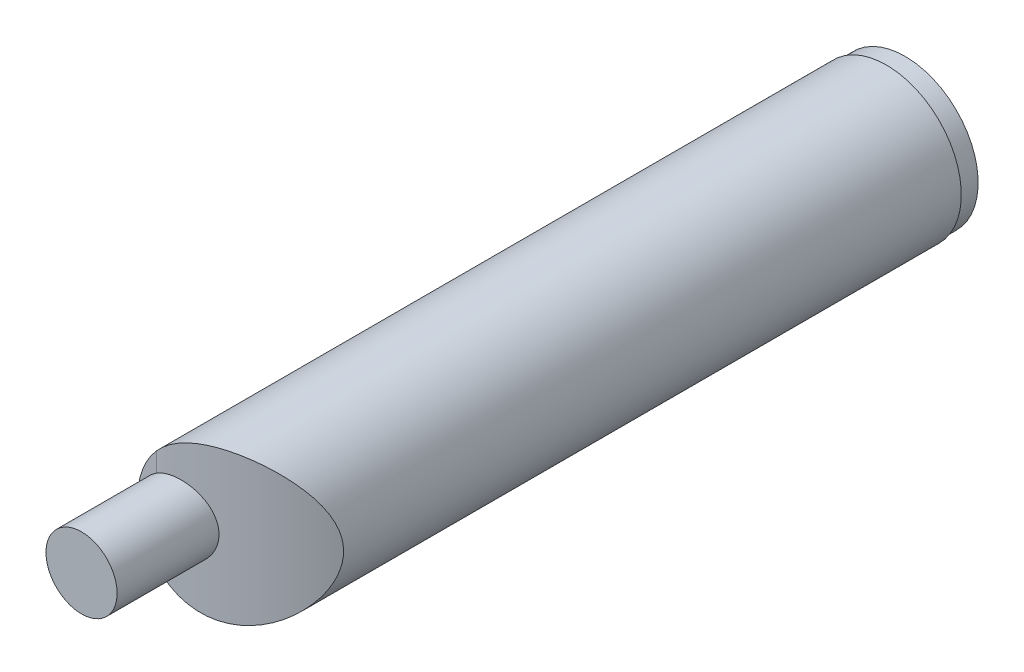
SolidWorks part; units mm, degrees
ref_plane "前视基准面" through (0, 0, 0) normal (0, 0, 1) x (1, 0, 0)
ref_plane "上视基准面" through (0, 0, 0) normal (0, 1, 0) x (1, 0, 0)
ref_plane "右视基准面" through (0, 0, 0) normal (1, 0, 0) x (0, 0, -1)
sketch "草图1" plane through (0, 0, 0) normal (0, 0, 1) x (1, 0, 0)
  circle A0 centre (0, 0) radius 4
  dimension "D1" = 8
extrude "凸台-拉伸1" add sketch "草图1" along normal blind 37
sketch "草图2" plane through (0, 0, 0) normal (0, 0, -1) x (-1, 0, 0)
  circle A0 centre (0, 0) radius 0.5
  circle A1 centre (0, 0) radius 3.9
  circle A2 centre (0, 0) radius 4
  circle A3 centre (0, 0) radius 4 construction
  circle M1 centre (0, 0) radius 4
  dimension "D1" = 7.8
  dimension "D2" = 1
extrude "切除-拉伸1" cut sketch "草图2" against normal blind 1 contours A1 M1 | A0 region at (0, 0, 0) region at (3.9887, 0, 0)
sketch "草图3" plane through (0, 0, 0) normal (0, 1, 0) x (1, 0, 0)
  line L0 (-3, -37) -> (4, -37)
  line L1 (4, -37) -> (4, -34)
  line L2 (4, -37) -> (4, -1) construction
  line L3 (-4, -37) -> (4, -37) construction
  line L4 (-4, -1) -> (-4, -37) construction
  arc A0 (-3, -37) -> (4, -34) centre (-3, -27.3333) ccw
  dimension "D1" = 3
  dimension "D2" = 1
extrude "切除-拉伸2" cut sketch "草图3" against normal through all both and the other way through all
sketch "草图4" plane through (0, 0, 37) normal (0, 0, 1) x (1, 0, 0)
  circle A0 centre (-2, 0) radius 1.9
  dimension "D1" = 3.8
  dimension "D2" = 2
extrude "凸台-拉伸2" add sketch "草图4" against normal up to next and the other way blind 5
